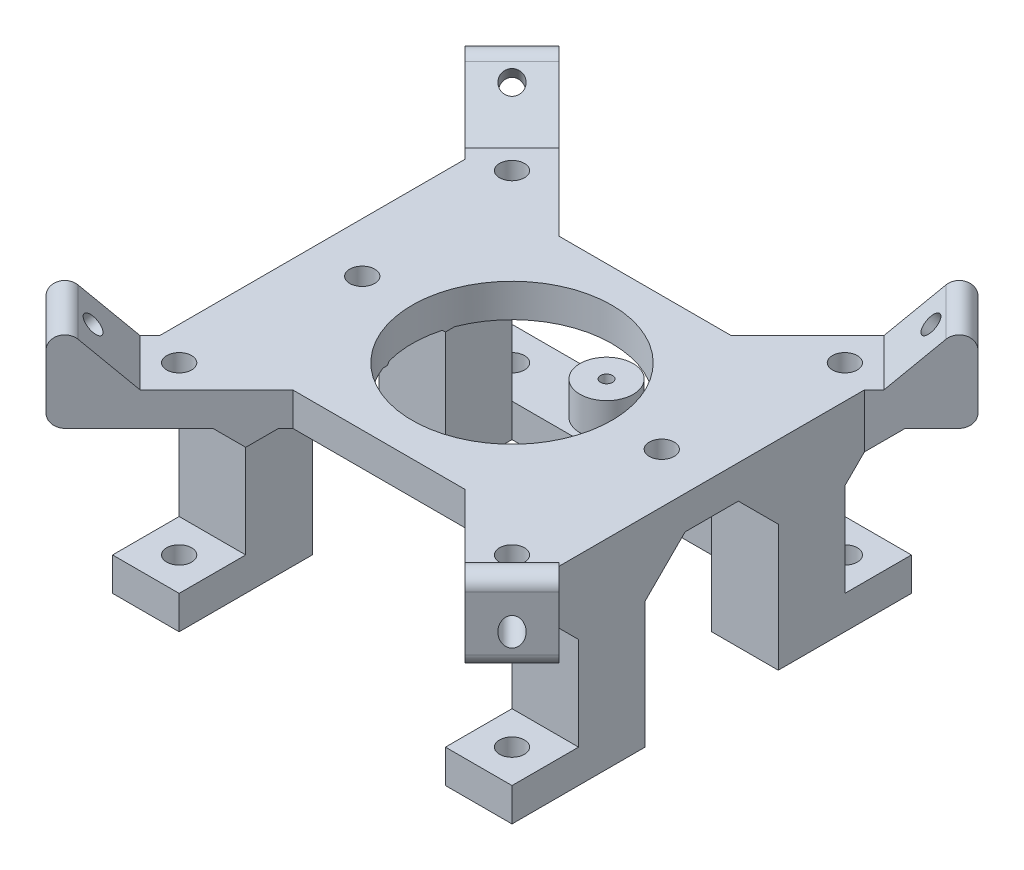
SolidWorks part; units mm, degrees
ref_plane "Front Plane" through (0, 0, 0) normal (0, 0, 1) x (1, 0, 0)
ref_plane "Top Plane" through (0, 0, 0) normal (0, 1, 0) x (1, 0, 0)
ref_plane "Right Plane" through (0, 0, 0) normal (1, 0, 0) x (0, 0, -1)
sketch "Sketch1" plane through (0, 0, 0) normal (0, 1, 0) x (1, 0, 0)
  line L1 (-30, -30) -> (30, -30)
  line L2 (-30, -30) -> (-30, 30)
  line L3 (-30, 30) -> (30, 30)
  line L4 (30, -30) -> (30, 30)
  line L5 (-30, -30) -> (30, 30) construction
  line L6 (-30, 30) -> (30, -30) construction
  point P0 (0, 0)
  dimension "D1" = 60
extrude "Boss-Extrude1" add sketch "Sketch1" along normal blind 5
sketch "Sketch2" plane through (0, 5, 0) normal (0, 1, 0) x (1, 0, 0)
  line L1 (-25, -25) -> (25, -25) construction
  line L2 (-25, -25) -> (-25, 25) construction
  line L3 (-25, 25) -> (25, 25) construction
  line L4 (25, -25) -> (25, 25) construction
  line L5 (-25, -25) -> (25, 25) construction
  line L6 (-25, 25) -> (25, -25) construction
  circle A0 centre (-25, 25) radius 1.875
  circle A1 centre (25, 25) radius 1.875
  circle A2 centre (25, -25) radius 1.875
  circle A3 centre (-25, -25) radius 1.875
  point P0 (0, 0)
  dimension "D2" = 3.75
  dimension "D1" = 50
extrude "Cut-Extrude1" cut sketch "Sketch2" against normal through all
sketch "Sketch3" plane through (0, 5, 0) normal (0, 1, 0) x (1, 0, 0)
  line L0 (0, 0) -> (50000, 0) construction
  line L1 (-20, 0) -> (-20, -50000) construction
  line L2 (20, 0) -> (20, -50000) construction
  line L3 (15.3779, 20) -> (50015.3779, 20) construction
  line L4 (15.3779, -20) -> (50015.3779, -20) construction
  line L5 (-30, 30) -> (-30, -30) construction
  line L6 (30, 30) -> (-30, 30) construction
  line L7 (30, -30) -> (30, 30) construction
  line L8 (-30, -30) -> (30, -30) construction
  line L10 (-20, -20) -> (-30, -20)
  line L11 (-20, -20) -> (-20, -10)
  line L12 (-20, -10) -> (-30, -10)
  line L13 (-30, -20) -> (-30, -10)
  line L14 (-20, 20) -> (-30, 20)
  line L15 (-20, 20) -> (-20, 10)
  line L16 (-20, 10) -> (-30, 10)
  line L17 (-30, 20) -> (-30, 10)
  line L18 (20, 20) -> (30, 20)
  line L19 (20, 20) -> (20, 10)
  line L20 (20, 10) -> (30, 10)
  line L21 (30, 20) -> (30, 10)
  line L22 (30, -20) -> (20, -20)
  line L23 (30, -20) -> (30, -10)
  line L24 (30, -10) -> (20, -10)
  line L25 (20, -20) -> (20, -10)
  dimension "D1" = 10
  dimension "D2" = 10
  dimension "D3" = 10
  dimension "D4" = 10
extrude "Boss-Extrude2" add sketch "Sketch3" along normal blind 20
sketch "Sketch4" plane through (0, 25, 0) normal (0, 1, 0) x (1, 0, 0)
  line L1 (30, 20) -> (-30, 20)
  line L2 (30, 20) -> (30, -20)
  line L3 (30, -20) -> (-30, -20)
  line L4 (-30, 20) -> (-30, -20)
extrude "Boss-Extrude3" add sketch "Sketch4" along normal blind 5
sketch "Sketch5" plane through (0, 5, 0) normal (0, 1, 0) x (1, 0, 0)
  line L0 (-20, -20) -> (-20, -30)
  line L1 (-20, -30) -> (20, -30)
  line L2 (20, -30) -> (20, -20)
  line L3 (20, 20) -> (20, 30)
  line L4 (20, 30) -> (-20, 30)
  line L5 (-20, 30) -> (-20, 20)
  line L20 (20, -10) -> (30, -10)
  line L21 (30, -10) -> (30, 10)
  line L22 (30, 10) -> (20, 10)
  line L23 (20, 10) -> (20, 20)
  line L24 (20, 20) -> (30, 20)
  line L25 (30, 20) -> (30, 30)
  line L26 (30, 30) -> (-30, 30)
  line L27 (-30, 30) -> (-30, 20)
  line L28 (-30, 20) -> (-20, 20)
  line L29 (-20, 20) -> (-20, 10)
  line L30 (-20, 10) -> (-30, 10)
  line L31 (-30, 10) -> (-30, -10)
  line L32 (-30, -10) -> (-20, -10)
  line L33 (-20, -10) -> (-20, -20)
  line L34 (-20, -20) -> (-30, -20)
  line L35 (-30, -20) -> (-30, -30)
  line L36 (-30, -30) -> (30, -30)
  line L37 (30, -30) -> (30, -20)
  line L38 (30, -20) -> (20, -20)
  line L39 (20, -20) -> (20, -10)
  line L40 (20, -10) -> (30, -10)
  line L41 (30, -10) -> (30, 10)
  line L42 (30, 10) -> (20, 10)
  line L43 (20, 10) -> (20, 20)
  line L44 (20, 20) -> (30, 20) construction
  line L45 (30, 20) -> (30, 30) construction
  line L46 (30, 30) -> (-30, 30) construction
  line L47 (-30, 30) -> (-30, 20) construction
  line L48 (-30, 20) -> (-20, 20) construction
  line L49 (-20, 20) -> (-20, 10)
  line L50 (-20, 10) -> (-30, 10)
  line L51 (-30, 10) -> (-30, -10)
  line L52 (-30, -10) -> (-20, -10)
  line L53 (-20, -10) -> (-20, -20)
  line L54 (-20, -20) -> (-30, -20) construction
  line L55 (-30, -20) -> (-30, -30) construction
  line L56 (-30, -30) -> (30, -30) construction
  line L57 (30, -30) -> (30, -20) construction
  line L58 (30, -20) -> (20, -20) construction
  line L59 (20, -20) -> (20, -10)
  dimension "D1" = 0
extrude "Cut-Extrude2" cut sketch "Sketch5" against normal blind 5
sketch "Sketch9" plane through (0, 30, 0) normal (0, 1, 0) x (1, 0, 0)
  line L0 (5.1625, 5.1625) -> (-35350.1766, -35350.1766) construction
  line L1 (0, 0) -> (-35355.3391, 35355.3391) construction
  line L2 (38.5355, -31.4645) -> (31.4645, -38.5355)
  line L3 (35, 35) -> (-35, 35) construction
  line L4 (35, 35) -> (35, -35) construction
  line L5 (35, -35) -> (-35, -35) construction
  line L6 (-35, 35) -> (-35, -35) construction
  line L7 (35, 35) -> (-35, -35) construction
  line L8 (35, -35) -> (-35, 35) construction
  line L9 (-31.4645, -38.5355) -> (-38.5355, -31.4645)
  line L11 (-31.4645, 38.5355) -> (-38.5355, 31.4645)
  line L12 (38.5355, 31.4645) -> (31.4645, 38.5355)
  line L13 (31.4645, -38.5355) -> (12.9289, -20)
  line L14 (-30, -20) -> (30, -20) construction
  line L15 (38.5355, -31.4645) -> (30, -22.9289)
  line L16 (30, -20) -> (30, 20) construction
  line L17 (38.5355, 31.4645) -> (30, 22.9289)
  line L18 (31.4645, 38.5355) -> (12.9289, 20)
  line L19 (30, 20) -> (-30, 20) construction
  line L20 (-31.4645, 38.5355) -> (-12.9289, 20)
  line L21 (-38.5355, 31.4645) -> (-30, 22.9289)
  line L22 (-30, 20) -> (-30, -20) construction
  line L23 (-38.5355, -31.4645) -> (-30, -22.9289)
  line L24 (-31.4645, -38.5355) -> (-12.9289, -20)
  line L25 (-12.9289, 20) -> (12.9289, 20)
  line L26 (30, 22.9289) -> (30, -22.9289)
  line L27 (12.9289, -20) -> (-12.9289, -20)
  line L28 (-30, 22.9289) -> (-30, -22.9289)
  point P5 (0, 0)
  point P13 (35, -35)
  point P16 (-35, -35)
  point P19 (-35, 35)
  point P22 (35, 35)
  dimension "D1" = 70
  dimension "D2" = 10
extrude "Boss-Extrude6" add sketch "Sketch9" against normal blind 5
sketch "Sketch10" plane through (-3.5355, 0, -3.5355) normal (-0.7071, 0, -0.7071) x (-0.7071, 0, 0.7071)
  line L0 (49.4975, 30) -> (49.4975, 40)
  line L1 (49.4975, 40) -> (39.4975, 30)
  line L2 (37.4264, 30) -> (49.4975, 30) construction
  line L3 (39.4975, 30) -> (49.4975, 30)
  dimension "D1" = 10
extrude "Boss-Extrude7" add sketch "Sketch10" against normal up to surface (10 mm away) up to face at (-22.1967, 27.5, 29.2678)
sketch "Sketch11" plane through (-3.5355, 0, 3.5355) normal (-0.7071, 0, 0.7071) x (0.7071, 0, 0.7071)
  line L0 (-49.4975, 30) -> (-49.4975, 40)
  line L1 (-49.4975, 40) -> (-39.4975, 30)
  line L2 (-49.4975, 30) -> (-37.4264, 30) construction
  line L3 (-39.4975, 30) -> (-49.4975, 30)
  dimension "D1" = 10
extrude "Boss-Extrude8" add sketch "Sketch11" against normal up to surface (10 mm away) up to face at (-22.1967, 27.5, -29.2678)
sketch "Sketch12" plane through (3.5355, 0, -3.5355) normal (0.7071, 0, -0.7071) x (-0.7071, 0, -0.7071)
  line L0 (-49.4975, 30) -> (-49.4975, 40)
  line L1 (-49.4975, 40) -> (-39.4975, 30)
  line L2 (-49.4975, 30) -> (-37.4264, 30) construction
  line L3 (-39.4975, 30) -> (-49.4975, 30)
  dimension "D1" = 10
extrude "Boss-Extrude9" add sketch "Sketch12" against normal up to surface (10 mm away) up to face at (22.1967, 27.5, 29.2678)
sketch "Sketch13" plane through (-3.5355, 0, -3.5355) normal (-0.7071, 0, -0.7071) x (-0.7071, 0, 0.7071)
  line L0 (-49.4975, 30) -> (-49.4975, 40)
  line L1 (-49.4975, 40) -> (-39.4975, 30)
  line L2 (-49.4975, 30) -> (-23.2843, 30) construction
  line L3 (-39.4975, 30) -> (-49.4975, 30)
  dimension "D1" = 10
extrude "Boss-Extrude10" add sketch "Sketch13" against normal up to surface (10 mm away) up to face at (34.2678, 27.5, -27.1967)
sketch "Sketch14" plane through (3.3579, -4.7487, -3.3579) normal (-0.5, 0.7071, 0.5) x (0.866, 0.4082, 0.2887)
  line L0 (28.3722, 48.7846) -> (36.5372, 43.0111) construction
  line L1 (24.2897, 43.0111) -> (32.4547, 54.5581) construction
  line L2 (32.4547, 37.2376) -> (40.6197, 48.7846) construction
  circle A0 centre (32.4547, 45.8979) radius 1.5
  dimension "D1" = 3
extrude "Cut-Extrude3" cut sketch "Sketch14" against normal through all
sketch "Sketch15" plane through (3.3579, -4.7487, 3.3579) normal (-0.5, 0.7071, -0.5) x (0.866, 0.4082, -0.2887)
  line L0 (36.5372, -43.0111) -> (28.3722, -48.7846) construction
  line L1 (32.4547, -37.2376) -> (40.6197, -48.7846) construction
  line L2 (24.2897, -43.0111) -> (32.4547, -54.5581) construction
  circle A0 centre (32.4547, -45.8979) radius 1.5
  dimension "D1" = 3
extrude "Cut-Extrude4" cut sketch "Sketch15" against normal through all
sketch "Sketch16" plane through (-3.3579, -4.7487, 3.3579) normal (0.5, 0.7071, -0.5) x (0.866, -0.4082, 0.2887)
  line L0 (-28.3722, -48.7846) -> (-36.5372, -43.0111) construction
  line L1 (-32.4547, -54.5581) -> (-24.2897, -43.0111) construction
  line L2 (-40.6197, -48.7846) -> (-32.4547, -37.2376) construction
  circle A0 centre (-32.4547, -45.8979) radius 1.5
  dimension "D1" = 3
extrude "Cut-Extrude5" cut sketch "Sketch16" against normal through all
sketch "Sketch17" plane through (-3.3579, -4.7487, -3.3579) normal (0.5, 0.7071, 0.5) x (0.866, -0.4082, -0.2887)
  line L0 (-36.5372, 43.0111) -> (-28.3722, 48.7846) construction
  line L1 (-32.4547, 37.2376) -> (-40.6197, 48.7846) construction
  line L2 (-24.2897, 43.0111) -> (-32.4547, 54.5581) construction
  circle A0 centre (-32.4547, 45.8979) radius 1.5
  dimension "D1" = 3
extrude "Cut-Extrude6" cut sketch "Sketch17" against normal through all
sketch "Sketch21" plane through (0, 25, 0) normal (0, -1, 0) x (1, 0, 0)
  circle A0 centre (0, 0) radius 15
  dimension "D1" = 30
extrude "Cut-Extrude7" cut sketch "Sketch21" against normal through all
chamfer "Chamfer1" distance 6 angle 45 12 edges at (25, 25, -20) (20, 25, -15) (25, 25, -10) (25, 25, 20) (25, 25, 10) (20, 25, 15) (-25, 25, -20) (-20, 25, -15) (-25, 25, -10) (-25, 25, 20) (-20, 25, 15) (-25, 25, 10)
fillet "Fillet1" radius 2 8 edges at (35, 25, 35) (35, 25, -35) (35, 40, -35) (35, 40, 35) (-35, 40, 35) (-35, 40, -35) (-35, 25, -35) (-35, 25, 35)
sketch "Sketch22" plane through (0, 0, 0) normal (0, -1, 0) x (1, 0, 0)
  line L0 (-20, -30) -> (-20, -10) construction
  line L1 (20, -30) -> (-20, -30)
  line L2 (20, -30) -> (20, -20)
  line L3 (20, -20) -> (-20, -20)
  line L4 (-20, -30) -> (-20, -20)
  line L5 (-20, -20) -> (-30, -20) construction
extrude "Boss-Extrude14" add sketch "Sketch22" against normal up to surface (5 mm away) up to face at (25, 5, -23.125)
sketch "Sketch23" plane through (0, 5, 0) normal (0, 1, 0) x (1, 0, 0)
  line L0 (0, 30) -> (0, 20) construction
  line L1 (30, 30) -> (-30, 30) construction
  line L2 (-20, 20) -> (20, 20) construction
  line L3 (10.795, 25) -> (-10.795, 25) construction
  circle A0 centre (10.795, 25) radius 0.9
  circle A1 centre (-10.795, 25) radius 0.9
  point P9 (0, 25)
  dimension "D2" = 1.8
  dimension "D1" = 21.59
extrude "Cut-Extrude8" cut sketch "Sketch23" against normal through all
sketch "Sketch24" plane through (0, 5, 0) normal (0, 1, 0) x (1, 0, 0)
  circle A0 centre (10.795, 25) radius 4
  circle A1 centre (-10.795, 25) radius 4
  circle A2 centre (10.795, 25) radius 0.9 construction
  circle A3 centre (-10.795, 25) radius 0.9 construction
  circle A4 centre (10.795, 25) radius 0.9
  circle A5 centre (-10.795, 25) radius 0.9
  dimension "D1" = 8
extrude "Boss-Extrude15" add sketch "Sketch24" along normal blind 5
sketch "Sketch25" plane through (0, 0, 0) normal (0, -1, 0) x (1, 0, 0)
  circle A0 centre (-25, 25) radius 1.875 construction
  circle A1 centre (-25, -25) radius 1.875 construction
  circle A2 centre (25, -25) radius 1.875 construction
  circle A3 centre (25, 25) radius 1.875 construction
  circle A4 centre (-25, 25) radius 1.875
  circle A5 centre (-25, -25) radius 1.875
  circle A6 centre (25, -25) radius 1.875
  circle A7 centre (25, 25) radius 1.875
extrude "Cut-Extrude9" cut sketch "Sketch25" against normal through all
sketch "Sketch26" plane through (0, 30, 0) normal (0, 1, 0) x (1, 0, 0)
  line L0 (15, 0) -> (30, 0) construction
  line L1 (30, -22.9289) -> (30, 22.9289) construction
  line L2 (-15, 0) -> (-30, 0) construction
  line L3 (-30, 22.9289) -> (-30, -22.9289) construction
  circle A0 centre (0, 0) radius 15 construction
  circle A1 centre (-22.5, 0) radius 1.875
  circle A2 centre (22.5, 0) radius 1.875
  dimension "D1" = 3.75
extrude "Cut-Extrude10" cut sketch "Sketch26" against normal through all
